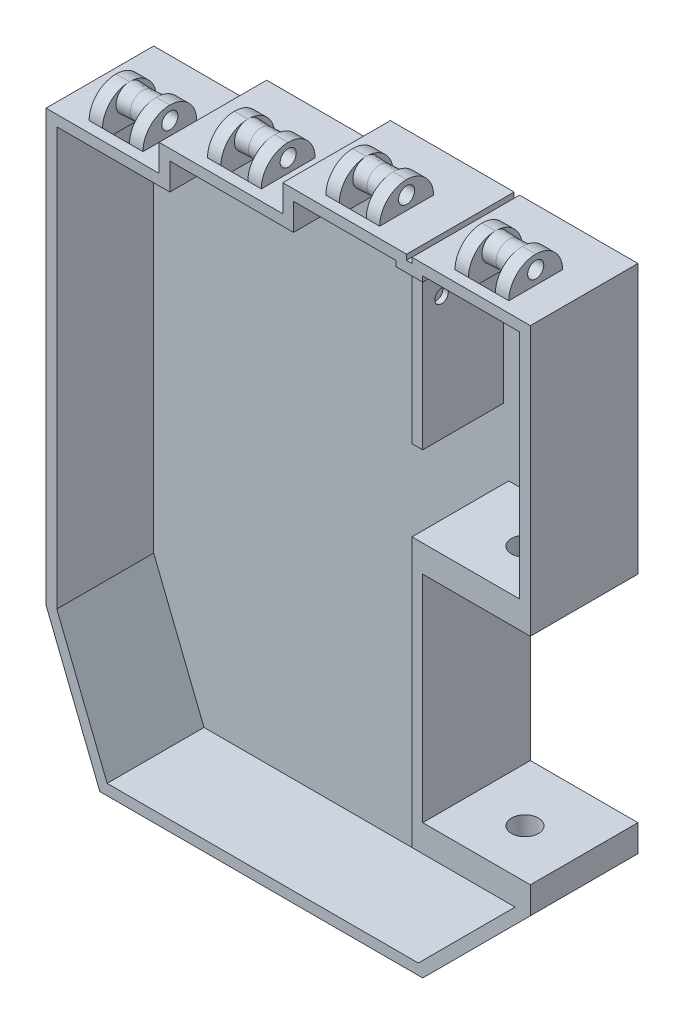
SolidWorks part; units mm, degrees
ref_plane "Front Plane" through (0, 0, 0) normal (0, 0, 1) x (1, 0, 0)
ref_plane "Top Plane" through (0, 0, 0) normal (0, 1, 0) x (1, 0, 0)
ref_plane "Right Plane" through (0, 0, 0) normal (1, 0, 0) x (0, 0, -1)
sketch "Sketch1" plane through (0, 0, 0) normal (0, 0, 1) x (1, 0, 0)
  line L0 (0, 0) -> (60, 0)
  line L1 (60, 0) -> (80, 20)
  line L2 (80, 20) -> (80, 115)
  line L3 (80, 115) -> (58, 115)
  line L4 (-10, 105) -> (11, 105)
  line L5 (-10, 105) -> (-10, 25)
  line L6 (-10, 25) -> (0, 0)
  line L7 (57, 115) -> (57, 114)
  line L8 (35, 115) -> (57, 115)
  line L9 (34, 115) -> (34, 110)
  line L10 (35, 115) -> (34, 115)
  line L11 (34, 110) -> (12, 110)
  line L12 (12, 110) -> (11, 110)
  line L13 (11, 110) -> (11, 105)
  line L14 (57, 115) -> (58, 115)
  line L15 (57, 114) -> (58, 114)
  line L16 (58, 114) -> (58, 115)
  dimension "D1" = 60
  dimension "D2" = 22
  dimension "D3" = 90
  dimension "D4" = 20
  dimension "D5" = 80
  dimension "D6" = 95
  dimension "D7" = 135
  dimension "D8" = 1
  dimension "D9" = 22
  dimension "D10" = 22
  dimension "D11" = 1
  dimension "D12" = 5
  dimension "D13" = 1
  dimension "D14" = 5
  dimension "D15" = 1
extrude "Boss-Extrude1" add sketch "Sketch1" along normal blind 20 contours L16 L15 L7 L8 L10 L9 L11 L12 L13 L4 L5 L6 L0 L1 L2 L3 region at (35.6394, 57.3872, 0)
sketch "Sketch2" plane through (0, 0, 20) normal (0, 0, 1) x (1, 0, 0)
  line L0 (80, 25) -> (60, 25)
  line L2 (60, 25) -> (60, 65)
  line L3 (60, 65) -> (80, 65)
  line L4 (80, 65) -> (80, 25)
  dimension "D1" = 20
  dimension "D2" = 5
  dimension "D3" = 40
extrude "Cut-Extrude1" cut sketch "Sketch2" against normal through all
shell "Shell1" thickness 2 removed face at (44.4444, 74.6111, 20)
sketch "Sketch34" plane through (0, 70, 0) normal (0, 1, 0) x (1, 0, 0)
  line L0 (58, -2) -> (58, -20) construction
  line L1 (78, -2) -> (58, -2) construction
  circle A0 centre (70, -11) radius 2.5
  dimension "D3" = 5
  dimension "D1" = 12
  dimension "D2" = 9
extrude "Cut-Extrude14" cut sketch "Sketch34" against normal up to surface (50 mm away) up to face at (67.5858, 20, 11)
sketch "Sketch3" plane through (0, 115, 0) normal (0, 1, 0) x (1, 0, 0)
  line L1 (80, 0) -> (58, 0) construction
  line L2 (74, -8) -> (64, -8)
  line L3 (74, -8) -> (74, -18)
  line L4 (74, -18) -> (64, -18)
  line L5 (64, -8) -> (64, -18)
  line L6 (74, -8) -> (64, -18) construction
  line L7 (74, -18) -> (64, -8) construction
  line L8 (66.5, -8) -> (66.5, -18)
  line L9 (71.5, -8) -> (71.5, -18)
  point P0 (69, -13)
  dimension "D1" = 10
  dimension "D2" = 10
  dimension "D3" = 5
  dimension "D4" = 2.5
  dimension "D5" = 13
extrude "Boss-Extrude2" add sketch "Sketch3" along normal blind 5 contours L8 L2 L5 L4 | L2 L9 L4 L3 region at (72.75, 115, 13) region at (65.25, 115, 13)
fillet "Fillet2" radius 5 4 edges at (65.25, 120, 8) (65.25, 120, 18) (72.75, 120, 8) (72.75, 120, 18)
sketch "Sketch6" plane through (74, 0, 0) normal (1, 0, 0) x (0, 0, -1)
  circle A0 centre (-13, 117.5) radius 1.5
  dimension "D1" = 3
  dimension "D2" = 2.5
  dimension "D3" = 0
extrude "Cut-Extrude3" cut sketch "Sketch6" against normal up to surface (10 mm away) up to face at (64, 117.357, 13)
sketch "Sketch21" plane through (66.5, 0, 0) normal (1, 0, 0) x (0, 0, -1)
  circle A0 centre (-13, 117.5) radius 1.5
  circle A1 centre (-13, 117.5) radius 2.5
  circle M1 centre (-13, 117.5) radius 1.5
  dimension "D1" = 5
extrude "Boss-Extrude10" add sketch "Sketch21" along normal blind 2.5 draft 3 contours A1 M1 region at (66.5, 117.5, 15.4293)
mirror "Mirror7" about plane through (69, 0, 0) normal (1, 0, 0) of "Boss-Extrude10"
sketch "Sketch26" plane through (0, 115, 0) normal (0, 1, 0) x (1, 0, 0)
  line L1 (66.5, -18) -> (71.5, -18)
  line L2 (66.5, -18) -> (66.5, -8)
  line L3 (66.5, -8) -> (71.5, -8)
  line L4 (71.5, -18) -> (71.5, -8)
  dimension "D1" = 5
  dimension "D2" = 10
extrude "Cut-Extrude8" cut sketch "Sketch26" against normal up to surface (2 mm away) up to face at (69, 113, 11)
sketch "Sketch7" plane through (0, 115, 0) normal (0, 1, 0) x (1, 0, 0)
  line L0 (50, -8) -> (40, -8)
  line L1 (50, -8) -> (50, -18)
  line L2 (50, -18) -> (40, -18)
  line L3 (40, -8) -> (40, -18)
  line L4 (50, -8) -> (40, -18) construction
  line L5 (50, -18) -> (40, -8) construction
  line L6 (42.5, -8) -> (42.5, -18)
  line L7 (47.5, -8) -> (47.5, -18)
  line L10 (34, 0) -> (57, 0) construction
  point P0 (45, -13)
  dimension "D1" = 10
  dimension "D2" = 10
  dimension "D3" = 5
  dimension "D4" = 2.5
  dimension "D5" = 13
extrude "Boss-Extrude4" add sketch "Sketch7" along normal blind 5 contours L6 L0 L3 L2 | L0 L7 L2 L1 region at (48.75, 115, 13) region at (41.25, 115, 13)
fillet "Fillet4" radius 5 4 edges at (41.25, 120, 8) (41.25, 120, 18) (48.75, 120, 8) (48.75, 120, 18)
sketch "Sketch22" plane through (42.5, 0, 0) normal (1, 0, 0) x (0, 0, -1)
  circle A0 centre (-13, 117.5) radius 2.5
  dimension "D1" = 5
  dimension "D2" = 2.5
  dimension "D3" = 0
extrude "Boss-Extrude11" add sketch "Sketch22" along normal blind 2.5 draft 3
mirror "Mirror8" about plane through (45, 117.5, 13) normal (1, 0, 0) of "Boss-Extrude11"
sketch "Sketch23" plane through (50, 0, 0) normal (1, 0, 0) x (0, 0, -1)
  circle A0 centre (-13, 117.5) radius 1.5
  dimension "D3" = 3
  dimension "D1" = 0
  dimension "D2" = 2.5
extrude "Cut-Extrude7" cut sketch "Sketch23" against normal up to surface (10 mm away) up to face at (40, 117.357, 13)
sketch "Sketch27" plane through (0, 115, 0) normal (0, 1, 0) x (1, 0, 0)
  line L1 (42.5, -18) -> (47.5, -18)
  line L2 (42.5, -18) -> (42.5, -8)
  line L3 (42.5, -8) -> (47.5, -8)
  line L4 (47.5, -18) -> (47.5, -8)
  dimension "D1" = 5
  dimension "D2" = 10
extrude "Cut-Extrude9" cut sketch "Sketch27" against normal up to surface (2 mm away) up to face at (45.5, 113, 11)
sketch "Sketch10" plane through (0, 110, 0) normal (0, 1, 0) x (1, 0, 0)
  line L0 (28, -8) -> (18, -8)
  line L1 (28, -8) -> (28, -18)
  line L2 (28, -18) -> (18, -18)
  line L3 (18, -8) -> (18, -18)
  line L4 (28, -8) -> (18, -18) construction
  line L5 (28, -18) -> (18, -8) construction
  line L6 (20.5, -8) -> (20.5, -18)
  line L7 (25.5, -8) -> (25.5, -18)
  line L8 (34, 0) -> (11, 0) construction
  line L10 (34, -20) -> (34, 0) construction
  point P0 (23, -13)
  point P11 (22.5, 0)
  dimension "D1" = 10
  dimension "D2" = 10
  dimension "D3" = 5
  dimension "D4" = 2.5
  dimension "D5" = 13
  dimension "D6" = 11
extrude "Boss-Extrude6" add sketch "Sketch10" along normal blind 5 contours L6 L0 L3 L2 | L0 L7 L2 L1 region at (26.75, 110, 13) region at (19.25, 110, 13)
fillet "Fillet6" radius 5 4 edges at (19.25, 115, 18) (19.25, 115, 8) (26.75, 115, 8) (26.75, 115, 18)
sketch "Sketch28" plane through (20.5, 0, 0) normal (1, 0, 0) x (0, 0, -1)
  circle A0 centre (-13, 112.5) radius 2.5
  dimension "D3" = 5
  dimension "D1" = 2.5
  dimension "D2" = 0
extrude "Boss-Extrude12" add sketch "Sketch28" along normal blind 2.5 draft 3
mirror "Mirror9" about plane through (23, 112.5, 13) normal (1, 0, 0) of "Boss-Extrude12"
sketch "Sketch29" plane through (28, 0, 0) normal (1, 0, 0) x (0, 0, -1)
  circle A0 centre (-13, 112.5) radius 1.5
  dimension "D3" = 3
  dimension "D1" = 2.5
  dimension "D2" = 0
extrude "Cut-Extrude10" cut sketch "Sketch29" against normal up to surface (10 mm away) up to face at (18, 112.357, 13)
sketch "Sketch30" plane through (0, 110, 0) normal (0, 1, 0) x (1, 0, 0)
  line L1 (20.5, -18) -> (25.5, -18)
  line L2 (20.5, -18) -> (20.5, -8)
  line L3 (20.5, -8) -> (25.5, -8)
  line L4 (25.5, -18) -> (25.5, -8)
  dimension "D1" = 5
  dimension "D2" = 10
extrude "Cut-Extrude11" cut sketch "Sketch30" against normal up to surface (2 mm away) up to face at (24.5, 108, 11)
sketch "Sketch13" plane through (0, 105, 0) normal (0, 1, 0) x (1, 0, 0)
  line L0 (6, -8) -> (-4, -8)
  line L1 (6, -8) -> (6, -18)
  line L2 (6, -18) -> (-4, -18)
  line L3 (-4, -8) -> (-4, -18)
  line L4 (6, -8) -> (-4, -18) construction
  line L5 (6, -18) -> (-4, -8) construction
  line L6 (-1.5, -8) -> (-1.5, -18)
  line L7 (3.5, -8) -> (3.5, -18)
  line L8 (-10, 0) -> (11, 0) construction
  line L9 (-10, -20) -> (-10, 0) construction
  point P0 (1, -13)
  dimension "D1" = 10
  dimension "D2" = 10
  dimension "D3" = 5
  dimension "D4" = 2.5
  dimension "D5" = 13
  dimension "D6" = 11
extrude "Boss-Extrude8" add sketch "Sketch13" along normal blind 5 contours L6 L0 L3 L2 | L0 L7 L2 L1 region at (4.75, 105, 13) region at (-2.75, 105, 13)
fillet "Fillet8" radius 5 4 edges at (-2.75, 110, 18) (-2.75, 110, 8) (4.75, 110, 8) (4.75, 110, 18)
sketch "Sketch31" plane through (-1.5, 0, 0) normal (1, 0, 0) x (0, 0, -1)
  circle A0 centre (-13, 107.5) radius 2.5
  dimension "D3" = 5
  dimension "D1" = 2.5
  dimension "D2" = 0
extrude "Boss-Extrude13" add sketch "Sketch31" along normal blind 2.5 draft 3
mirror "Mirror10" about plane through (1, 107.5, 13) normal (1, 0, 0) of "Boss-Extrude13"
sketch "Sketch32" plane through (6, 0, 0) normal (1, 0, 0) x (0, 0, -1)
  circle A0 centre (-13, 107.5) radius 1.5
  dimension "D2" = 3
  dimension "D1" = 2.5
extrude "Cut-Extrude12" cut sketch "Sketch32" against normal up to surface (10 mm away) up to face at (-4, 107.357, 13)
sketch "Sketch33" plane through (0, 105, 0) normal (0, 1, 0) x (1, 0, 0)
  line L1 (-1.5, -8) -> (3.5, -8)
  line L2 (-1.5, -8) -> (-1.5, -18)
  line L3 (-1.5, -18) -> (3.5, -18)
  line L4 (3.5, -8) -> (3.5, -18)
  dimension "D1" = 5
  dimension "D2" = 10
extrude "Cut-Extrude13" cut sketch "Sketch33" against normal up to surface (2 mm away) up to face at (2.5, 103, 11)
sketch "Sketch37" plane through (78, 0, 0) normal (-1, 0, 0) x (0, 0, 1)
  line L0 (2, 105) -> (13.5, 105)
  line L1 (2, 70) -> (2, 113) construction
  line L2 (20, 113) -> (2, 113) construction
  dimension "D1" = 8
  dimension "D2" = 11.5
sketch "Sketch38" plane through (0, 0, 2) normal (0, 0, 1) x (1, 0, 0)
  line L0 (57, 82) -> (57, 112)
  line L1 (55, 112) -> (60, 112) construction
  line L2 (57, 112) -> (55, 112)
  line L3 (55, 112) -> (55, 82)
  line L4 (55, 82) -> (57, 82)
  line L5 (78, 70) -> (78, 113) construction
  dimension "D1" = 30
  dimension "D2" = 2
  dimension "D3" = 21
extrude "Boss-Extrude14" add sketch "Sketch38" along normal blind 15
sketch "Sketch39" plane through (0, 0, 2) normal (0, 0, 1) x (1, 0, 0)
  line L0 (66, 98.2) -> (66, 100.2)
  line L1 (69, 98.2) -> (57, 98.2) construction
  line L2 (66, 100.2) -> (71, 100.2)
  line L3 (71, 100.2) -> (71, 90.2)
  line L4 (71, 90.2) -> (69, 90.2)
  line L5 (69, 98.2) -> (69, 89.2) construction
  line L6 (69, 90.2) -> (69, 98.2)
  line L7 (69, 98.2) -> (66, 98.2)
  dimension "D1" = 3
  dimension "D2" = 2
  dimension "D3" = 5
  dimension "D4" = 8
extrude "Boss-Extrude15" add sketch "Sketch39" along normal blind 5
sketch "Sketch40" plane through (57, 0, 0) normal (1, 0, 0) x (0, 0, -1)
  circle A0 centre (-13.5, 105) radius 1.25
  dimension "D1" = 2.5
extrude "Cut-Extrude15" cut sketch "Sketch40" against normal blind 1 and the other way blind 21
